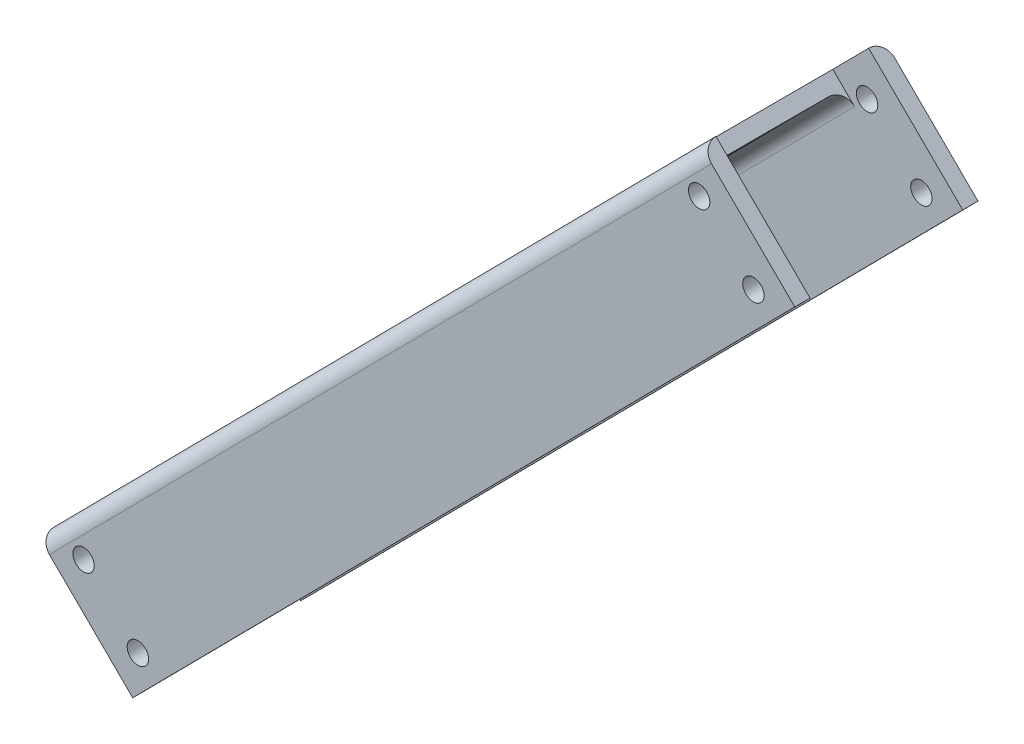
SolidWorks part; units mm, degrees
ref_plane "Front Plane" through (0, 0, 0) normal (0, 0, 1) x (1, 0, 0)
ref_plane "Top Plane" through (0, 0, 0) normal (0, 1, 0) x (1, 0, 0)
ref_plane "Right Plane" through (0, 0, 0) normal (1, 0, 0) x (0, 0, -1)
sketch "Sketch2" plane through (0, 0, 0) normal (0, 0, 1) x (1, 0, 0)
  line L0 (165.715, 148.457) -> (35.6364, 16.9102)
  line L1 (35.6364, 16.9102) -> (54.1241, -1.3711)
  line L4 (54.1241, -1.3711) -> (184.2027, 130.1757)
  line L25 (165.715, 148.457) -> (184.2027, 130.1757)
extrude "Boss-Extrude1" add sketch "Sketch2" against normal blind 3
sketch "Sketch4" plane through (0, 0, -36) normal (0, 0, -1) x (-1, 0, 0)
  line L6 (-165.715, 148.457) -> (-184.2027, 130.1757)
  line L9 (-184.2027, 130.1757) -> (-54.1241, -1.3711)
  line L10 (-54.1241, -1.3711) -> (-35.6364, 16.9102)
  line L11 (-35.6364, 16.9102) -> (-165.715, 148.457)
  line L12 (-165.715, 148.457) -> (-184.2027, 130.1757)
  line L15 (-184.2027, 130.1757) -> (-54.1241, -1.3711)
  line L16 (-54.1241, -1.3711) -> (-35.6364, 16.9102)
  line L17 (-35.6364, 16.9102) -> (-165.715, 148.457)
  dimension "D1" = 0
extrude "Boss-Extrude2" add sketch "Sketch4" against normal blind 3 separate body
sketch "Sketch5" plane through (0, 0, -3) normal (0, 0, -1) x (-1, 0, 0)
  line L0 (-35.6364, 16.9102) -> (-165.715, 148.457) construction
  line L1 (-35.6364, 16.9102) -> (-165.715, 148.457)
  line L2 (-37.7696, 14.8008) -> (-167.8482, 146.3476)
  line L3 (-37.7696, 14.8008) -> (-35.6364, 16.9102)
  line L4 (-167.8482, 146.3476) -> (-165.715, 148.457)
  dimension "D1" = 3
extrude "Boss-Extrude3" add sketch "Sketch5" along normal up to surface (30 mm away) up to face at (109.9195, 73.543, -33)
fillet "Fillet1" radius 3 4 edges at (102.8089, 80.5742, -3) (102.8089, 80.5742, -33) (100.6757, 82.6836, -36) (100.6757, 82.6836, 0)
sketch "Sketch6" plane through (9.5636, -9.4569, 0) normal (-0.7111, 0.7031, 0) x (0, 0, 1)
  circle A0 centre (-18, 197.0812) radius 7.5
extrude "Cut-Extrude1" cut sketch "Sketch6" against normal up to surface (3 mm away) up to face at (102.8089, 80.5742, -18)
sketch "Sketch7" plane through (9.5636, -9.4569, 0) normal (-0.7111, 0.7031, 0) x (0, 0, 1)
  line L5 (-3, 37.0812) -> (-3, 222.0812) construction
  line L6 (-3, 212.0812) -> (-3, 222.0812)
  line L7 (-33, 222.0812) -> (-33, 37.0812) construction
  line L8 (-33, 222.0812) -> (-33, 212.0812)
  line L9 (-33, 212.0812) -> (-3, 212.0812)
  line L12 (-33, 222.0812) -> (-3, 222.0812)
  line L13 (-36, 129.5812) -> (0, 129.5812) construction
  line L14 (-36, 37.0812) -> (-36, 222.0812) construction
  line L15 (0, 222.0812) -> (0, 37.0812) construction
  line L16 (-33, 37.0812) -> (-3, 37.0812)
  line L17 (-33, 47.0812) -> (-3, 47.0812)
  line L18 (-33, 37.0812) -> (-33, 47.0812)
  line L19 (-3, 47.0812) -> (-3, 37.0812)
extrude "Cut-Extrude2" cut sketch "Sketch7" against normal up to surface (26 mm away) up to face at (119.1634, 64.4023, -1.5)
sketch "Sketch8" plane through (0, 0, 0) normal (0, 0, 1) x (1, 0, 0)
  line L0 (58.6944, 3.2508) -> (40.2067, 21.5321) construction
  line L5 (179.6323, 125.5538) -> (161.1447, 143.8351) construction
  line L6 (158.6837, 141.3464) -> (165.715, 148.457) construction
  line L8 (100.6757, 82.6836) -> (119.1634, 64.4023) construction
  line L9 (42.6677, 24.0208) -> (158.6837, 141.3464) construction
  line L10 (54.1241, -1.3711) -> (184.2027, 130.1757) construction
  circle A0 centre (176.077, 129.0694) radius 2.1
  circle A1 centre (165.4111, 139.6163) radius 2.1
  circle A2 centre (44.4731, 17.3134) radius 2.1
  circle A3 centre (55.1391, 6.7664) radius 2.1
extrude "Cut-Extrude3" cut sketch "Sketch8" against normal up to surface (36 mm away) up to face at (110.9861, 72.4883, -36)
fillet "Fillet2" radius 1 2 edges at (142.8634, 125.3474, -18) (144.9966, 123.2381, -18)
